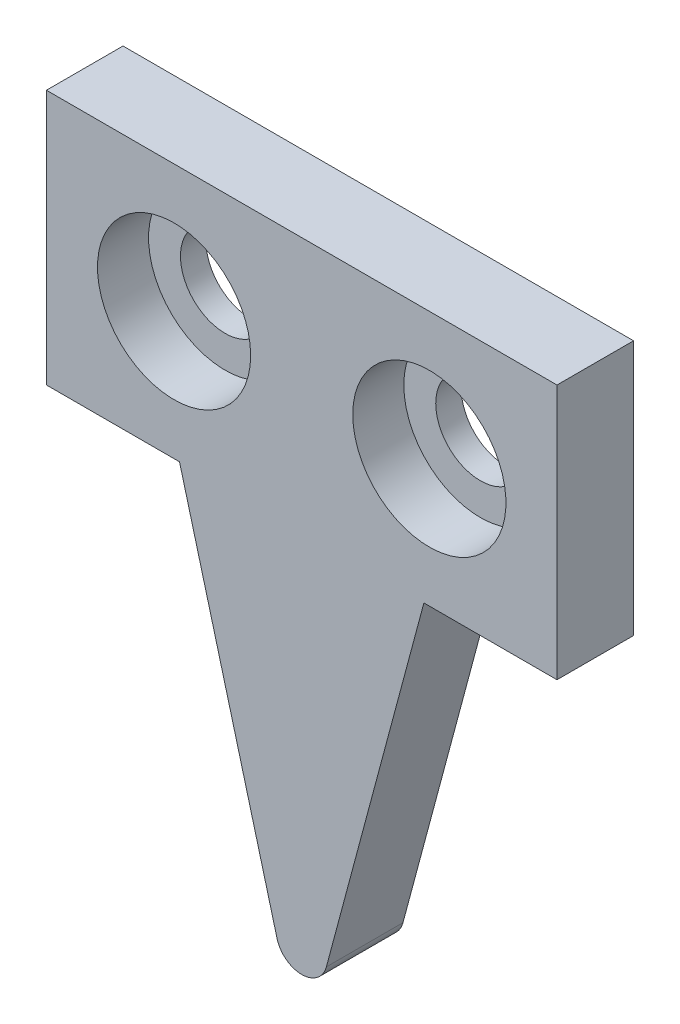
SolidWorks part; units mm, degrees
ref_plane "Front Plane" through (0, 0, 0) normal (0, 0, 1) x (1, 0, 0)
ref_plane "Top Plane" through (0, 0, 0) normal (0, 1, 0) x (1, 0, 0)
ref_plane "Right Plane" through (0, 0, 0) normal (1, 0, 0) x (0, 0, -1)
sketch "Sketch2" plane through (0, 0, 0) normal (0, 0, 1) x (1, 0, 0)
  line L1 (-4.7866, 14) -> (-0.9659, -0.2588)
  line L3 (0, -11.1651) -> (0, 29.6028) construction
  line L6 (-4.7866, 14) -> (-10, 14)
  line L7 (-10, 14) -> (-10, 24)
  line L8 (-10, 24) -> (10, 24)
  line L9 (10, 14) -> (10, 24)
  line L10 (4.7866, 14) -> (10, 14)
  line L11 (4.7866, 14) -> (0.9659, -0.2588)
  arc A0 (-0.9659, -0.2588) -> (0.9659, -0.2588) centre (0, 0) ccw
  point P5 (0, 24)
  point P11 (0, 24)
  point P13 (0, -1)
  dimension "D4" = 1
  dimension "D1" = 10
  dimension "D2" = 15
  dimension "D3" = 20
  dimension "D5" = 105
extrude "Boss-Extrude1" add sketch "Sketch2" along normal blind 3
sketch "Sketch3" plane through (0, 0, 3) normal (0, 0, 1) x (1, 0, 0)
  line L3 (-10, 24) -> (-10, 14) construction
  line L4 (0, -1) -> (0, 24) construction
  line L5 (10, 24) -> (-10, 24) construction
  circle A0 centre (-5, 19) radius 1.75
  arc A1 (-0.9659, -0.2588) -> (0.9659, -0.2588) centre (0, 0) ccw construction
  circle A2 centre (5, 19) radius 1.75
  point P9 (-10, 19)
  dimension "D1" = 3.5
  dimension "D2" = 5
  dimension "D3" = 5
extrude "Cut-Extrude1" cut sketch "Sketch3" against normal up to surface (3 mm away) up to face at (0, 12.8426, 0)
sketch "Sketch5" plane through (0, 0, 3) normal (0, 0, 1) x (1, 0, 0)
  line L0 (0, -1) -> (0, 24) construction
  line L1 (10, 24) -> (-10, 24) construction
  line L2 (-10, 24) -> (-10, 14) construction
  arc A0 (-0.9659, -0.2588) -> (0.9659, -0.2588) centre (0, 0) ccw construction
  circle A1 centre (-5, 19) radius 3
  circle A2 centre (5, 19) radius 3
  point P12 (-10, 19)
  dimension "D1" = 6
  dimension "D2" = 5
extrude "Cut-Extrude2" cut sketch "Sketch5" against normal blind 2
